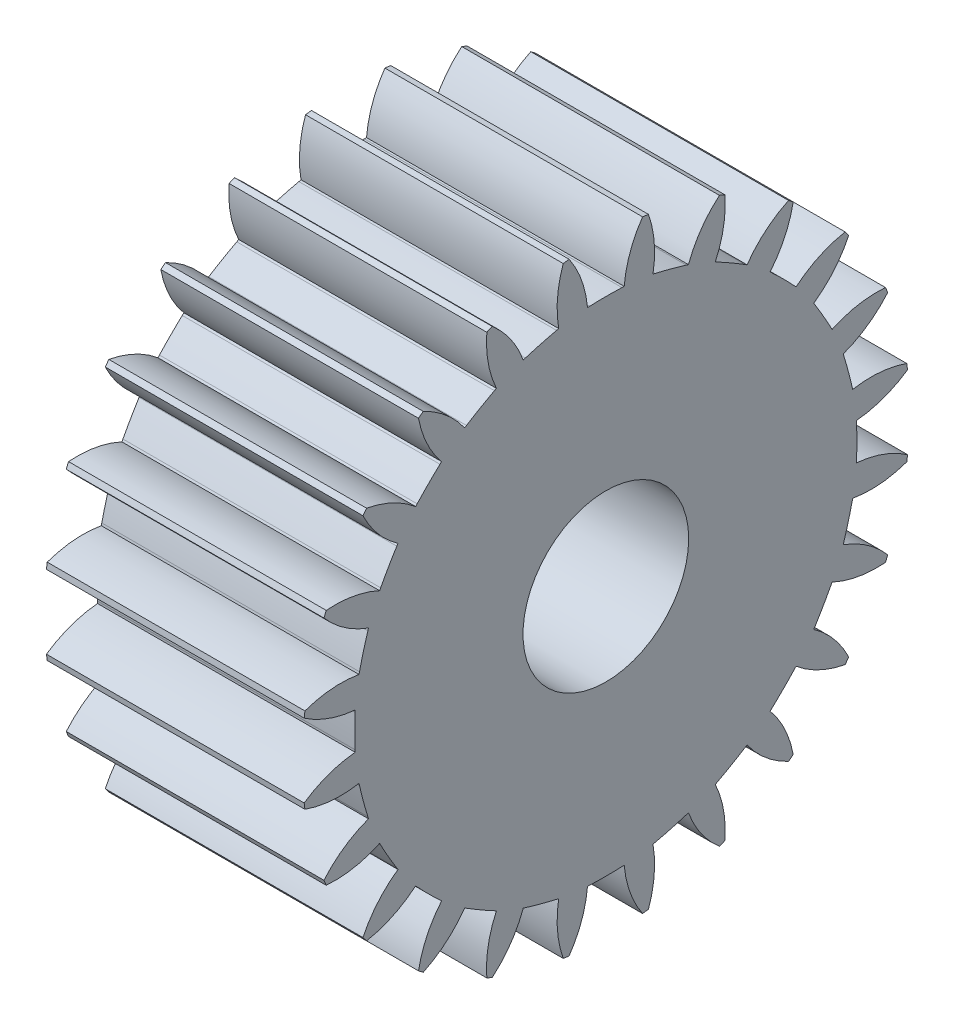
SolidWorks part; units mm, degrees
ref_plane "Front Plane" through (0, 0, 0) normal (0, 0, 1) x (1, 0, 0)
ref_plane "Top Plane" through (0, 0, 0) normal (0, 1, 0) x (1, 0, 0)
ref_plane "Right Plane" through (0, 0, 0) normal (1, 0, 0) x (0, 0, -1)
sketch "Sketch1" plane through (0, 0, 0) normal (1, 0, 0) x (0, 0, -1)
  circle A0 centre (0, 0) radius 82.55
  dimension "D1" = 165.1
extrude "Boss-Extrude1" add sketch "Sketch1" along normal mid plane 70
sketch "Sketch6" plane through (35, 0, 0) normal (1, 0, 0) x (0, 0, -1)
  circle A0 centre (0, 0) radius 22.5
  dimension "D1" = 45
extrude "Cut-Extrude4" cut sketch "Sketch6" against normal through all
sketch "Sketch7" plane through (35, 0, 0) normal (1, 0, 0) x (0, 0, -1)
  line L0 (0, 0) -> (0, 136.53) construction
  line L1 (0, 68.265) -> (-4.985, 68.0827)
  line L2 (0, 68.265) -> (4.985, 68.0827)
  line L3 (-9.975, 81.9451) -> (0, 96.1018)
  line L4 (9.975, 81.9451) -> (0, 96.1018)
  circle A0 centre (0, 0) radius 68.265 construction
  circle A1 centre (0, 0) radius 76.2 construction
  arc A2 (-4.985, 68.0827) -> (-9.975, 81.9451) centre (-33.8203, 65.5323) ccw
  circle A3 centre (0, 0) radius 82.55 construction
  arc A4 (4.985, 68.0827) -> (9.975, 81.9451) centre (33.8203, 65.5323) cw
  point P12 (0, 68.265)
  point P16 (0, 96.1018)
  dimension "D1" = 152.4
  dimension "D2" = 136.53
  dimension "D3" = 4.99
  dimension "D4" = 19.95
extrude "Cut-Extrude5" cut sketch "Sketch7" against normal through all
fillet "Fillet1" radius 120 1 edges at (0, 68.265, 0)
pattern_circular "CirPattern1" count 24 over 360 about axis through (35, 0, 0) along (1, 0, 0) of "Fillet1", "Cut-Extrude5"
